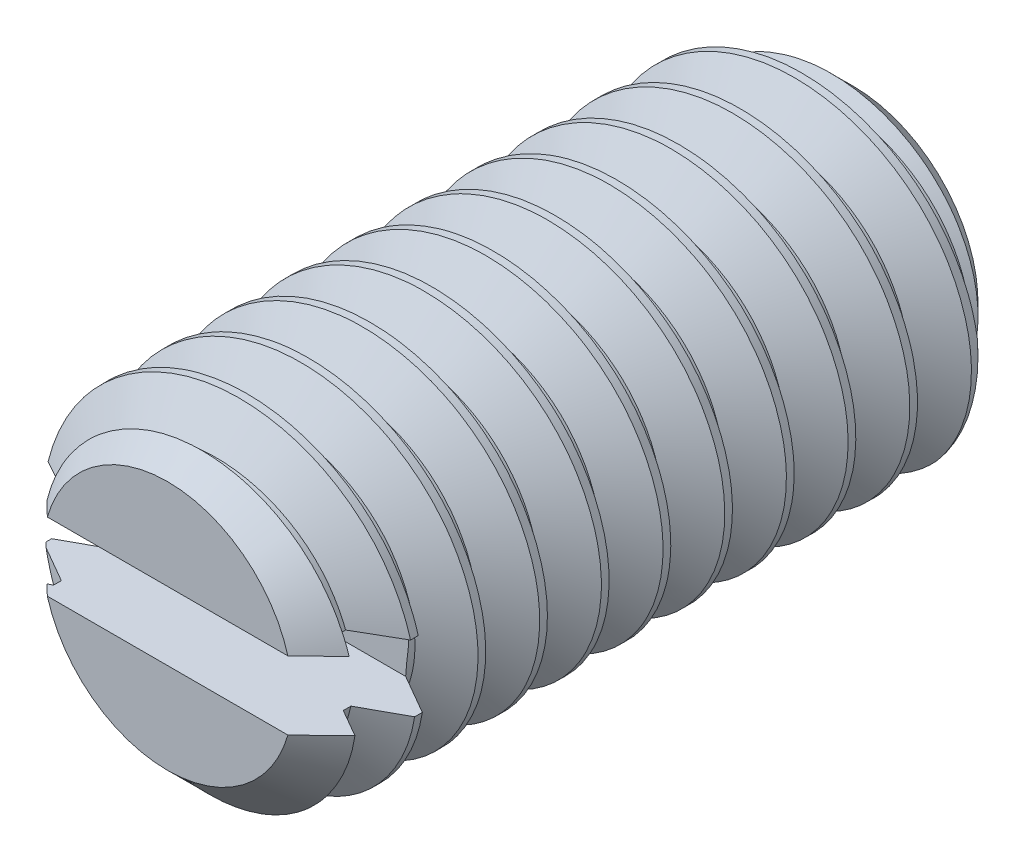
SolidWorks part; units mm, degrees
ref_plane "Front" through (0, 0, 0) normal (0, 0, 1) x (1, 0, 0)
ref_plane "Top" through (0, 0, 0) normal (0, 1, 0) x (1, 0, 0)
ref_plane "Right" through (0, 0, 0) normal (1, 0, 0) x (0, 0, -1)
sketch "Sketch1" plane through (0, 0, 0) normal (1, 0, 0) x (0, 0, -1)
  line L1 (2.5, 0) -> (-2.5, 0) construction
  line L3 (-2.5, 0) -> (-2.5, 0.9125) construction
  line L6 (-2.5, 0.9125) -> (-2.1625, 1.25) construction
  line L8 (-2.9219, 1.2987) -> (-2.4719, 1.2987) construction
  line L10 (-2.4719, 1.2987) -> (-2.6969, 0.909) construction
  line L11 (-2.6969, 0.909) -> (-2.9219, 1.2987) construction
  line L12 (-2.6969, 0.909) -> (-2.6969, 0.9577) construction
  line L13 (-2.725, 0.9577) -> (-2.6687, 0.9577) construction
  line L14 (-2.8937, 1.25) -> (-2.5, 1.25) construction
  line L15 (-2.6969, 1.2987) -> (-2.6969, 1.25) construction
  line L16 (-2.9078, 1.2744) -> (-2.4859, 1.2744) construction
  line L17 (-2.1625, 1.25) -> (2.1625, 1.25) construction
  line L18 (2.1625, 1.25) -> (2.5, 0.9125) construction
  line L19 (2.5, 0.9125) -> (2.5, 0) construction
  line L21 (-1.7, -0.25) -> (-2.5, -0.25)
  line L22 (-1.7, -0.25) -> (-1.7, 0.25)
  line L23 (-1.7, 0.25) -> (-2.5, 0.25)
  line L24 (-2.5, -0.25) -> (-2.5, 0.25)
  line L25 (-2.1, 0.25) -> (-2.1, -0.25) construction
  line L26 (-1.7, 0) -> (-2.5, 0) construction
  point P0 (-2.1, 0)
  point P3 (0, 0)
  point P22 (-2.6969, 0.9577)
  point P25 (-2.6969, 1.25)
  point P28 (-2.6969, 1.2744)
  point P32 (-0.925, 1.25)
  point P36 (-0.925, -1.25)
  dimension "Thread Pitch" = 0.45
  dimension "D5" = 0.0563
  dimension "Length" = 5
  dimension "D1" = 45
  dimension "Thread Size" = 2.5
  dimension "D2" = 0.3375
  dimension "Slot Height" = 0.5
  dimension "Slot Depth" = 0.8
  dimension "D3" = 1.575
sketch "Sketch2" plane through (0, 0, 0) normal (1, 0, 0) x (0, 0, -1)
  line L0 (-2.5, 0) -> (-2.5, 0.9125)
  line L1 (-2.5, 0.9125) -> (-2.1625, 1.25)
  line L2 (-2.1625, 1.25) -> (2.1625, 1.25)
  line L3 (2.1625, 1.25) -> (2.5, 0.9125)
  line L4 (2.5, 0.9125) -> (2.5, 0)
  line L5 (2.5, 0) -> (-2.5, 0)
revolve "Revolve1" add sketch "Sketch2" angle 360 about L5
sketch "Sketch3" plane through (0, 0, 0) normal (1, 0, 0) x (0, 0, -1)
  line L1 (-2.5, 0.25) -> (-1.7, 0.25)
  line L2 (-2.5, 0.25) -> (-2.5, -0.25)
  line L3 (-2.5, -0.25) -> (-1.7, -0.25)
  line L4 (-1.7, 0.25) -> (-1.7, -0.25)
extrude "Cut-Extrude1" cut sketch "Sketch3" against normal through all both and the other way through all
sketch "Sketch4" plane through (0, 0, 2.5) normal (0, 0, 1) x (1, 0, 0)
  line L0 (0, 0.25) -> (0, -0.25) construction
  circle A0 centre (0, 0) radius 1.25
curve "Helix/Spiral1" pitch 0.45 height 5.45 radius 1.25 centre (0, 0, 2.5) axis (0, 0, -1) start towards (0, 1, 0)
sketch "Sketch5" plane through (0, 0, 0) normal (1, 0, 0) x (0, 0, -1)
  line L0 (-2.9078, 1.2744) -> (-2.4859, 1.2744)
  line L1 (-2.4859, 1.2744) -> (-2.6687, 0.9577)
  line L2 (-2.4719, 1.2987) -> (-2.6969, 0.909) construction
  line L3 (-2.6687, 0.9577) -> (-2.725, 0.9577)
  line L4 (-2.725, 0.9577) -> (-2.9078, 1.2744)
sweep "Cut-Sweep1" cut profiles "Sketch5" path "Helix/Spiral1"
equation "\"D2@Sketch1\"=\"Thread Pitch@Sketch1\"*.75"
equation "\"D3@Helix/Spiral1\"=\"Length@Sketch1\"+\"D4@Helix/Spiral1\""
equation "\"D4@Helix/Spiral1\"=\"Thread Pitch@Sketch1\""
equation "\"D5@Sketch1\"=\"Thread Pitch@Sketch1\"/8"
equation "\"D3@Sketch1\"=\"Thread Pitch@Sketch1\"*3.5"
